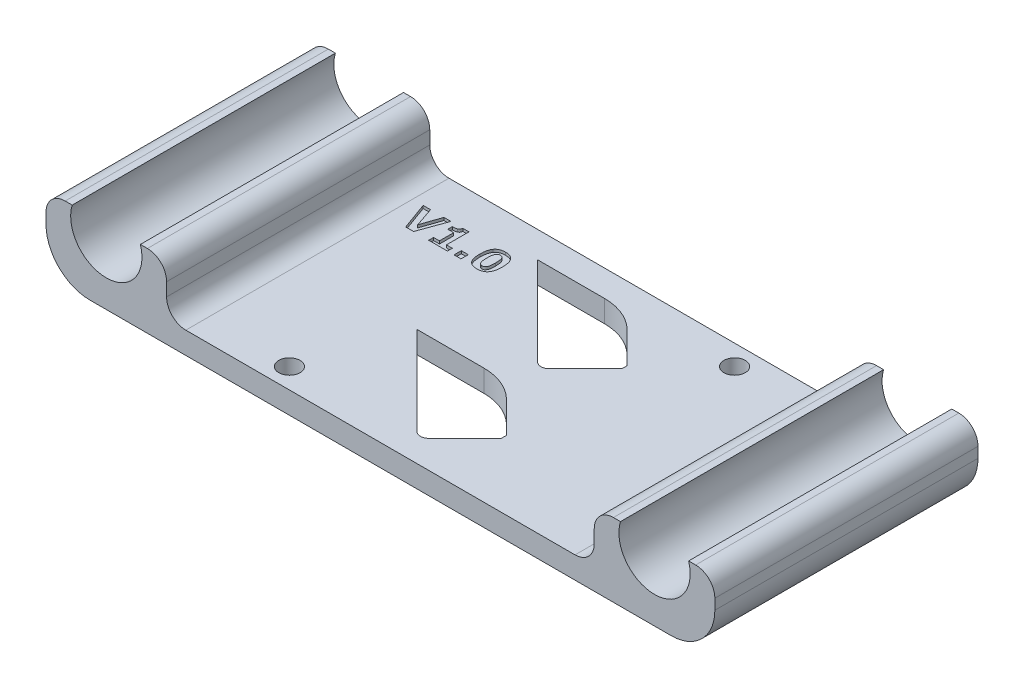
SolidWorks part; units mm, degrees
ref_plane "Front Plane" through (0, 0, 0) normal (0, 0, 1) x (1, 0, 0)
ref_plane "Top Plane" through (0, 0, 0) normal (0, 1, 0) x (1, 0, 0)
ref_plane "Right Plane" through (0, 0, 0) normal (1, 0, 0) x (0, 0, -1)
sketch "Sketch1" plane through (0, 0, 0) normal (0, 0, 1) x (1, 0, 0)
  line L0 (0, 13.4) -> (4.7839, 13.4)
  line L1 (0, 13.4) -> (0, 0)
  line L2 (122, 13.4) -> (122, 0)
  line L4 (117.2161, 13.4) -> (122, 13.4)
  line L5 (100, 13.4) -> (100, 4)
  line L6 (22, 4) -> (22, 13.4)
  line L7 (22, 4) -> (100, 4)
  line L8 (17.2161, 13.4) -> (22, 13.4)
  line L9 (11, 13.4) -> (11, 11.5) construction
  line L10 (11, 11.5) -> (111, 11.5) construction
  line L13 (100, 13.4) -> (104.7839, 13.4)
  line L18 (0, 0) -> (122, 0)
  arc A0 (104.7839, 13.4) -> (117.2161, 13.4) centre (111, 11.5) ccw
  arc A1 (4.7839, 13.4) -> (17.2161, 13.4) centre (11, 11.5) ccw
  dimension "D6" = 6.5
  dimension "D5" = 22
  dimension "D1" = 7.5
  dimension "D2" = 4
  dimension "D3" = 100
  dimension "D4" = 22
  dimension "D7" = 1.9
  dimension "D8" = 11
extrude "Boss-Extrude1" add sketch "Sketch1" along normal blind 48
fillet "Fillet1" radius 3.5 6 edges at (0, 13.4, 24) (22, 4, 24) (22, 13.4, 24) (100, 4, 24) (100, 13.4, 24) (122, 13.4, 24)
fillet "Fillet2" radius 8 2 edges at (122, 0, 24) (0, 0, 24)
ref_plane "Plane1" through (0, 0, 24) normal (0, 0, -1) x (-1, 0, 0)
ref_plane "Plane2" through (61, 0, 0) normal (-1, 0, 0) x (0, 0, 1)
sketch "Sketch6" plane through (0, 0, 0) normal (0, -1, 0) x (1, 0, 0)
  circle A0 centre (40.7, 44.3) radius 1.95
  circle A1 centre (81.3, 3.7) radius 1.95
  point P0 (40.7, 44.3)
  point P1 (81.3, 3.7)
  dimension "D1" = 3.9
extrude "Cut-Extrude2" cut sketch "Sketch6" against normal blind 6
sketch "Sketch7" plane through (0, 0, 0) normal (0, -1, 0) x (1, 0, 0)
  line L0 (63.6751, 44) -> (46.477, 26.8018)
  line L1 (71.3683, 36.3068) -> (63.6751, 44)
  line L2 (62.8027, 26.8018) -> (71.3683, 35.3675)
  line L3 (71.3683, 35.3675) -> (71.3683, 36.3068)
  line L4 (46.477, 26.8018) -> (62.8027, 26.8018)
  line L7 (8, 48) -> (114, 48) construction
  dimension "D1" = 45
  dimension "D2" = 45
  dimension "D3" = 90
  dimension "D4" = 4
extrude "Cut-Extrude3" cut sketch "Sketch7" against normal through all
pattern_linear "LPattern1" count 2 spacing 22 along (0, 0, -1) of "Cut-Extrude3"
fillet "Fillet3" radius 10 2 edges at (62.8027, 2, 26.8018) (62.8027, 2, 4.8018)
sketch "Sketch8" plane through (0, 0, 0) normal (1, 0, 0) x (0, 0, -1)
  line L5 (0, 0) -> (-48, 0) construction
  line L8 (-24, 0) -> (-24, -16.902) construction
  line L9 (-24, -22.0879) -> (-24, 22.0879) construction
  line L10 (-11, -0.25) -> (-13.5, -0.25)
  line L11 (-11, -2.25) -> (-13.5, -2.25)
  line L12 (-13.5, -4) -> (-10.7126, -4)
  line L13 (-13.5, -0.25) -> (-13.5, 0)
  line L14 (-13.5, 0) -> (-5, 0)
  line L15 (-13.5, -4) -> (-13.5, -2.25)
  line L16 (-5, 0) -> (-10.7126, -4)
  arc A1 (-11, -0.25) -> (-11, -2.25) centre (-11, -1.25) cw
extrude "Boss-Extrude2" add sketch "Sketch8" along normal blind 12 from offset 20
fillet "Fillet4" radius 3 2 edges at (26, -4, 10.7126) (26, 0, 5)
fillet "Fillet5" radius 0.5 2 edges at (26, -2.25, 13.5) (26, -4, 13.5)
pattern_linear "LPattern2" count 3 spacing 12 along (0, 0, 1) of "Boss-Extrude2", "Fillet4", "Fillet5"
sketch "Sketch9" plane through (0, 0, 0) normal (0, 0, -1) x (-1, 0, 0)
  line L0 (-32, 0) -> (-29.5, -4)
  line L1 (-8, 0) -> (-114, 0) construction
  line L2 (-29.5, -4) -> (-32, -4)
  line L3 (-32, -4) -> (-32, 0)
  line L4 (-20, 0) -> (-22.5, -4)
  line L5 (-22.5, -4) -> (-20, -4)
  line L6 (-20, -4) -> (-20, 0)
  line L7 (-20, -4) -> (-32, -4) construction
  line L8 (-20, -3.4575) -> (-20, -0.5425) construction
  line L9 (-32, -3.4575) -> (-32, -0.5425) construction
  dimension "D1" = 2.5
  dimension "D2" = 2.5
extrude "Cut-Extrude4" cut sketch "Sketch9" against normal through all
sketch "Sketch10" plane through (0, 4, 0) normal (0, 1, 0) x (1, 0, 0)
  text T0 "V1.0" font "Verdana" height 5
extrude "Cut-Extrude5" cut sketch "Sketch10" against normal blind 0.5
sketch "Sketch11" plane through (0, 0, 0) normal (0, -1, 0) x (1, 0, 0)
  line L1 (38.7, 40.3) -> (42.7, 40.3)
  line L2 (38.7, 40.3) -> (38.7, 5.3)
  line L3 (38.7, 5.3) -> (42.7, 5.3)
  line L4 (42.7, 40.3) -> (42.7, 5.3)
  line L5 (78.3, 4.7) -> (73.3, 4.7)
  line L6 (78.3, 4.7) -> (78.3, 22.7)
  line L7 (78.3, 22.7) -> (73.3, 22.7)
  line L8 (73.3, 4.7) -> (73.3, 22.7)
  line L9 (40.7, 40.3) -> (40.7, 44.3) construction
  point P12 (81.3, 3.7)
  dimension "D1" = 4
  dimension "D2" = 35
  dimension "D3" = 4
  dimension "D4" = 1
  dimension "D5" = 18
  dimension "D6" = 8
  dimension "D7" = 5
extrude "Cut-Extrude6" cut sketch "Sketch11" against normal blind 2.5
chamfer "Chamfer1" distance 1.5 angle 45 8 edges at (75.8, 0, 4.7) (78.3, 0, 13.7) (73.3, 0, 13.7) (75.8, 0, 22.7) (40.7, 0, 5.3) (42.7, 0, 22.8) (38.7, 0, 22.8) (40.7, 0, 40.3)
fillet "Fillet6" radius 1.5 2 edges at (63.6751, 2, 22) (63.6751, 2, 44)
sketch "Sketch12" plane through (0, 0, 0) normal (1, 0, 0) x (0, 0, -1)
  line L0 (-11, 0) -> (-13.5173, -3)
  line L1 (-4.0541, 0) -> (-13.5, 0) construction
  line L2 (-13.5173, -3) -> (-15.5173, -3)
  line L3 (-15.5173, -3) -> (-15.5173, 0)
  line L4 (0, 0) -> (-48, 0) construction
  line L5 (-15.5173, 0) -> (-11, 0)
  dimension "D1" = 50
  dimension "D2" = 11
  dimension "D3" = 2
  dimension "D4" = 3
extrude "Boss-Extrude3" add sketch "Sketch12" along normal blind 4 from offset 15
fillet "Fillet7" radius 1 2 edges at (15, -1.5, 12.2586) (19, -1.5, 12.2586)
fillet "Fillet8" radius 1 1 edges at (17, -3, 15.5173)
fillet "Fillet9" radius 1 5 edges at (19, 0, 13.9114) (18.7071, 0, 11.3823) (17, 0, 11) (15.2929, 0, 11.3823) (15, 0, 13.9114)
pattern_linear "LPattern3" count 3 spacing 12 along (0, 0, 1) of "Fillet9", "Boss-Extrude3", "Fillet8", "Fillet7"
